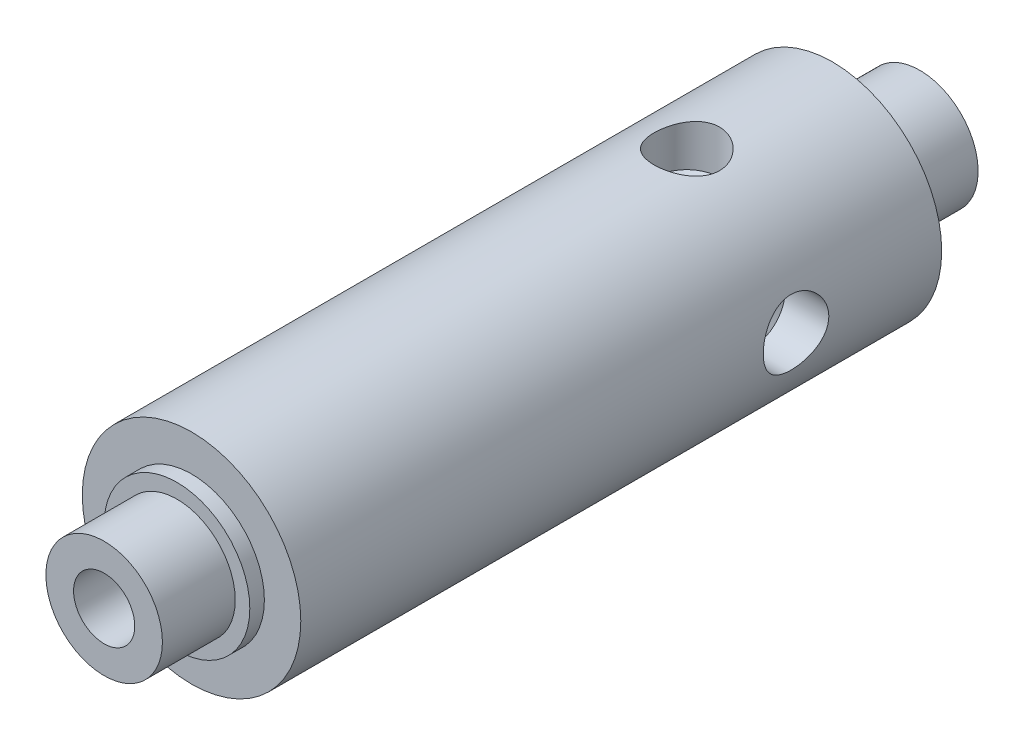
SolidWorks part; units mm, degrees
ref_plane "Спереди" through (0, 0, 0) normal (0, 0, 1) x (1, 0, 0)
ref_plane "Сверху" through (0, 0, 0) normal (0, 1, 0) x (1, 0, 0)
ref_plane "Справа" through (0, 0, 0) normal (1, 0, 0) x (0, 0, -1)
sketch "Эскиз1" plane through (0, 0, 0) normal (0, 0, 1) x (1, 0, 0)
  circle A0 centre (0, 0) radius 7.5
  dimension "D1" = 15
extrude "Бобышка-Вытянуть1" add sketch "Эскиз1" along normal blind 56
sketch "Эскиз2" plane through (0, 0, 56) normal (0, 0, 1) x (1, 0, 0)
  circle A0 centre (0, 0) radius 4
  circle A1 centre (0, 0) radius 7.5
  circle A2 centre (0, 0) radius 7.5 construction
  dimension "D1" = 8
extrude "Вырез-Вытянуть1" cut sketch "Эскиз2" against normal blind 6
sketch "Эскиз3" plane through (0, 0, 0) normal (0, 0, -1) x (-1, 0, 0)
  circle A0 centre (0, 0) radius 4
  circle A1 centre (0, 0) radius 7.5
  circle A2 centre (0, 0) radius 7.5 construction
  dimension "D1" = 8
extrude "Вырез-Вытянуть2" cut sketch "Эскиз3" against normal blind 6
hole_wizard "Отверстие обработанное метчиком M5x0.81" positions "Эскиз7" profile "Эскиз6" tap size "M5x0.8" standard "Ansi Metric"
sketch "Эскиз7" plane through (0, 0, 0) normal (0, 0, -1) x (-1, 0, 0)
  point P0 (0, 0)
sketch "Эскиз6" plane through (0, 0, 0) normal (1, 0, 0) x (0, 1, 0)
  line L0 (0, 0) -> (0, 11.2618)
  line L1 (0, 11.2618) -> (2.1, 10)
  line L2 (2.1, 10) -> (2.1, 0)
  line L5 (2.1, 0) -> (0, 0)
  line L10 (0, 11.2618) -> (-2.1, 10) construction
  line L11 (0, -6.35) -> (0, 107.95) construction
  dimension "Диаметр сверла" = 4.2
  dimension "Глубина сверла" = 10
  dimension "Угол заточки сверла" = 118
cosmetic thread "Отверстие резьбы1" parameters "D1"=10, "D2"=5
hole_wizard "Отверстие обработанное метчиком M5x0.82" positions "Эскиз9" profile "Эскиз8" tap size "M5x0.8" standard "Ansi Metric"
sketch "Эскиз9" plane through (0, 0, 56) normal (0, 0, 1) x (1, 0, 0)
  point P0 (0, 0)
sketch "Эскиз8" plane through (0, 0, 56) normal (1, 0, 0) x (0, -1, 0)
  line L0 (0, 0) -> (0, 11.2618)
  line L1 (0, 11.2618) -> (2.1, 10)
  line L2 (2.1, 10) -> (2.1, 0)
  line L5 (2.1, 0) -> (0, 0)
  line L10 (0, 11.2618) -> (-2.1, 10) construction
  line L11 (0, -6.35) -> (0, 107.95) construction
  dimension "Диаметр сверла" = 4.2
  dimension "Глубина сверла" = 10
  dimension "Угол заточки сверла" = 118
cosmetic thread "Отверстие резьбы2" parameters "D1"=10, "D2"=5
sketch "Эскиз12" plane through (0, 0, 6) normal (0, 0, -1) x (-1, 0, 0)
  circle A0 centre (0, 0) radius 4
  circle A1 centre (0, 0) radius 5
  circle A2 centre (0, 0) radius 4 construction
  dimension "D1" = 10
extrude "Бобышка-Вытянуть2" add sketch "Эскиз12" along normal blind 1
sketch "Эскиз13" plane through (0, 0, 50) normal (0, 0, 1) x (1, 0, 0)
  circle A0 centre (0, 0) radius 4
  circle A1 centre (0, 0) radius 5
  circle A2 centre (0, 0) radius 4 construction
  dimension "D1" = 10
extrude "Бобышка-Вытянуть3" add sketch "Эскиз13" along normal blind 1
ref_plane "Плоскость1" through (0, 0, 32) normal (0, 0, 1) x (1, 0, 0)
ref_plane "Плоскость3" through (0, 7.5, 0) normal (0, 1, 0) x (1, 0, 0)
sketch "Эскиз15" plane through (0, 7.5, 0) normal (0, 1, 0) x (1, 0, 0)
  line L0 (0, 0) -> (0, -56) construction
  line L1 (-4, -56) -> (4, -56) construction
  line L2 (-12.7244, -16) -> (13.4353, -16) construction
  line L3 (-19.919, -32) -> (19.919, -32) construction
  dimension "D1" = 16
hole_wizard "Отверстие с зазором M41" positions "Эскиз17" profile "Эскиз16" hole size "M4" standard "Ansi Metric"
sketch "Эскиз17" plane through (0, 7.5, 0) normal (0, 1, 0) x (1, 0, 0)
  line L0 (0, 0) -> (0, -56) construction
  line L1 (-12.7244, -16) -> (13.4353, -16) construction
  point P0 (0, -16)
sketch "Эскиз16" plane through (0, 7.5, 16) normal (1, 0, 0) x (0, 0, 1)
  line L0 (0, 0) -> (0, 4.3519)
  line L1 (0, 4.3519) -> (2.25, 3)
  line L2 (2.25, 3) -> (2.25, 0)
  line L5 (2.25, 0) -> (0, 0)
  line L10 (0, 4.3519) -> (-2.25, 3) construction
  line L11 (0, -6.35) -> (0, 107.95) construction
  dimension "Диаметр отверстия" = 4.5
  dimension "Глубина отверстия" = 3
  dimension "Угол заточки сверла" = 118
ref_plane "Плоскость4" through (7.5, 0, 0) normal (1, 0, 0) x (0, 0, -1)
sketch "Эскиз18" plane through (7.5, 0, 0) normal (1, 0, 0) x (0, 0, -1)
  line L0 (0, 0) -> (-56, 0) construction
  line L1 (-56, 4) -> (-56, -4) construction
  line L2 (-16, 11.033) -> (-16, -13.2488) construction
  line L3 (-32, 19.919) -> (-32, -19.919) construction
  dimension "D1" = 16
hole_wizard "Отверстие с зазором M42" positions "Эскиз20" profile "Эскиз19" hole size "M4" standard "Ansi Metric"
sketch "Эскиз20" plane through (7.5, 0, 0) normal (1, 0, 0) x (0, 0, -1)
  line L0 (0, 0) -> (-56, 0) construction
  line L1 (-16, 11.033) -> (-16, -13.2488) construction
  point P0 (-16, 0)
sketch "Эскиз19" plane through (7.5, 0, 16) normal (0, 1, 0) x (0, 0, -1)
  line L0 (0, 0) -> (0, 4.3519)
  line L1 (0, 4.3519) -> (2.25, 3)
  line L2 (2.25, 3) -> (2.25, 0)
  line L5 (2.25, 0) -> (0, 0)
  line L10 (0, 4.3519) -> (-2.25, 3) construction
  line L11 (0, -6.35) -> (0, 107.95) construction
  dimension "Диаметр отверстия" = 4.5
  dimension "Глубина отверстия" = 3
  dimension "Угол заточки сверла" = 118
